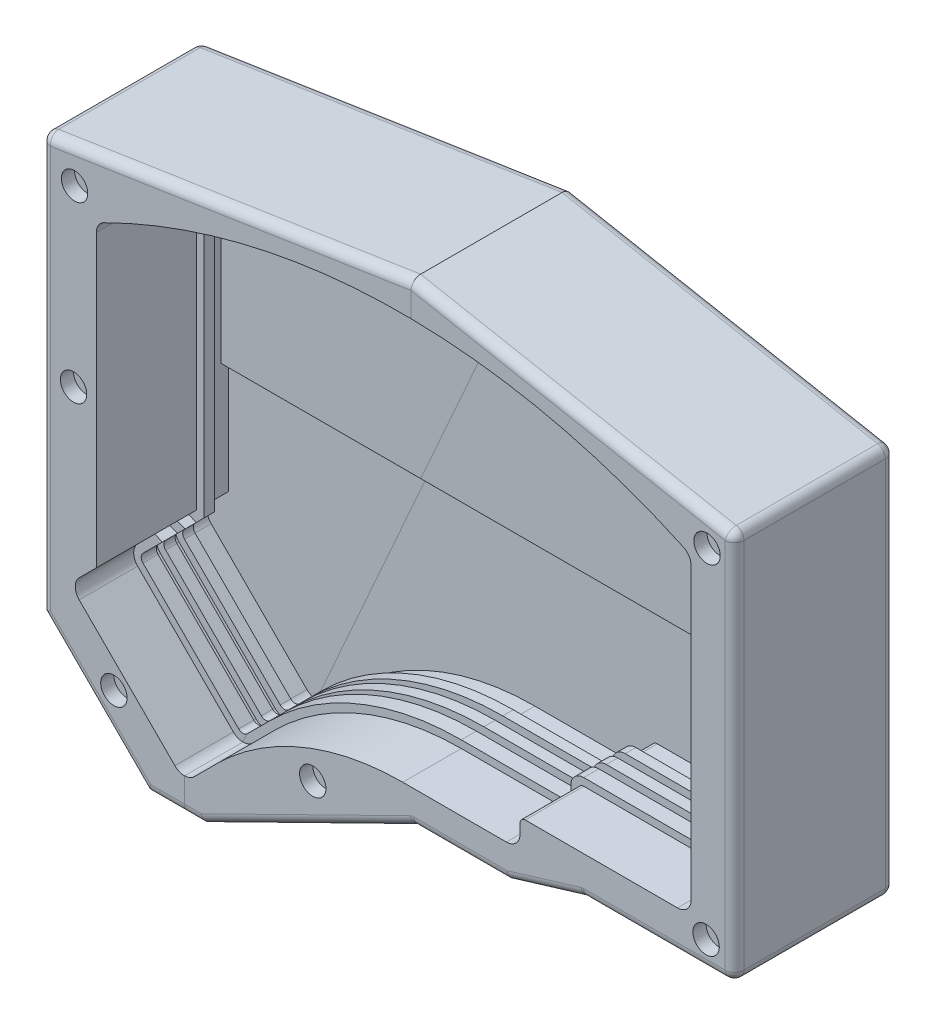
SolidWorks part; units mm, degrees
ref_plane "Front Plane" through (0, 0, 0) normal (0, 0, 1) x (1, 0, 0)
ref_plane "Top Plane" through (0, 0, 0) normal (0, 1, 0) x (1, 0, 0)
ref_plane "Right Plane" through (0, 0, 0) normal (1, 0, 0) x (0, 0, -1)
sketch "Base Drawing" plane through (0, 0, 0) normal (0, 0, 1) x (1, 0, 0)
  line B0 (121.2897, -20.025) -> (161.6756, -20.025)
  line B1 (164.2756, -17.425) -> (164.2756, 59.3777)
  line B2 (8.5386, 57.0643) -> (8.5386, -20.3999)
  line B3 (8.5386, -20.3999) -> (3.6971, -25.2415)
  line B4 (3.6971, -28.9184) -> (29.0822, -54.3036)
  line B5 (32.7591, -54.3036) -> (38.7165, -48.3462)
  line B6 (88.8147, -27.5948) -> (116.2897, -27.5948)
  line B7 (118.8897, -24.9948) -> (118.8897, -22.425)
  circle B8 centre (143.7256, 57.675) radius 1.125
  circle B9 centre (143.7256, 0.525) radius 1.125
  circle B10 centre (64.1715, 70.175) radius 1.125
  circle B11 centre (76.8847, -7.8268) radius 1.125
  circle B12 centre (121.0327, -10.1679) radius 1.125
  circle B13 centre (33.1742, -25.9322) radius 1.125
  arc B14 (161.6756, -20.025) -> (164.2756, -17.425) centre (161.6756, -17.425) ccw
  arc B15 (164.2756, 59.3777) -> (162.7654, 61.7383) centre (161.6756, 59.3777) ccw
  arc B16 (162.7654, 61.7383) -> (9.9768, 59.3903) centre (88.8147, -98.4444) ccw
  arc B17 (9.9768, 59.3903) -> (8.5386, 57.0643) centre (11.1386, 57.0643) ccw
  arc B18 (3.6971, -25.2415) -> (3.6971, -28.9184) centre (5.5355, -27.0799) ccw
  arc B19 (29.0822, -54.3036) -> (32.7591, -54.3036) centre (30.9207, -52.4651) ccw
  arc B20 (88.8147, -27.5948) -> (38.7165, -48.3462) centre (88.8147, -98.4444) ccw
  arc B21 (116.2897, -27.5948) -> (118.8897, -24.9948) centre (116.2897, -24.9948) ccw
  arc B22 (121.2897, -20.025) -> (118.8897, -22.425) centre (121.2897, -22.425) ccw
sketch_block_instance "Block1-1"
sketch_block "Block1"
sketch "Sketch2" plane through (0, 0, 0) normal (0, 0, 1) x (1, 0, 0)
  line L0 (164.2756, 20.9764) -> (176.7756, 20.9764) construction
  line L1 (164.2756, -17.425) -> (164.2756, 59.3777) construction
  line L2 (176.7756, 20.9764) -> (176.7756, 71.7383)
  line L3 (91.0386, 77.9706) -> (30.9207, -55.0651)
  line L4 (91.0386, 77.9706) -> (91.0386, 87.9706)
  line L5 (91.0386, 87.9706) -> (176.7756, 71.7383)
  line L6 (176.7756, 20.9764) -> (176.7756, -31.525)
  line L7 (176.7756, -31.525) -> (136.7756, -31.525)
  line L8 (136.7756, -31.525) -> (136.7756, -37.5948) construction
  line L9 (136.7756, -37.5948) -> (116.7756, -37.5948) construction
  line L10 (116.7756, -37.5948) -> (136.7756, -31.525)
  line L11 (30.9207, -55.0651) -> (30.9207, -65.0651)
  line L12 (116.7756, -37.5948) -> (91.7756, -37.5948)
  line L14 (30.9207, -55.0651) -> (35.9207, -55.0651) construction
  line L15 (-7.0645, 72.9201) -> (91.0386, 87.9706)
  line L16 (-7.0645, -27.0799) -> (-7.0645, 72.9201)
  line L17 (35.9207, -55.0651) -> (35.9207, -65.0651) construction
  line L18 (2.9355, -27.0799) -> (-7.0645, -27.0799) construction
  line L19 (91.7756, -37.5948) -> (35.9207, -65.0651)
  line L20 (-7.0645, -27.0799) -> (-7.0645, -37.0799)
  line L21 (30.9207, -65.0651) -> (20.9207, -65.0651)
  line L22 (20.9207, -65.0651) -> (-7.0645, -37.0799)
  line L23 (35.9207, -65.0651) -> (30.9207, -65.0651)
  arc A0 (162.7654, 61.7383) -> (9.9768, 59.3903) centre (88.8147, -98.4444) ccw construction
  arc A1 (29.0822, -54.3036) -> (32.7591, -54.3036) centre (30.9207, -52.4651) ccw construction
  arc A2 (3.6971, -25.2415) -> (3.6971, -28.9184) centre (5.5355, -27.0799) ccw construction
  dimension "D1" = 12.5
  dimension "D2" = 10
  dimension "D3" = 10
  dimension "D4" = 11.5
  dimension "D5" = 40
  dimension "D6" = 10
  dimension "D7" = 20
  dimension "D8" = 10
  dimension "D9" = 25
  dimension "D10" = 10
  dimension "D11" = 85.737
  dimension "D12" = 100
  dimension "D13" = 10
  dimension "D14" = 10
  dimension "D15" = 5
extrude "Boss-Extrude1" add sketch "Sketch2" along normal blind 35 and the other way blind 7.5 contours L22 L21 L11 L3 L4 L15 L20 | L12 L10 L7 L6 L2 L5 L4 L3 L11 region at (114.4551, 13.7405, 0) region at (31.2356, 22.7834, 0)
ref_plane "Plane1" through (0, 0, 0) normal (0, 0, -1) x (-1, 0, 0)
sketch "Cutout" plane through (0, 0, 0) normal (0, 0, -1) x (-1, 0, 0)
  line L9 (-118.8897, -24.9948) -> (-118.8897, -22.425)
  line L10 (-88.8147, -27.5948) -> (-116.2897, -27.5948)
  line L11 (-32.7591, -54.3036) -> (-38.7165, -48.3462)
  line L12 (-3.6971, -28.9184) -> (-29.0822, -54.3036)
  line L13 (-8.5386, -20.3999) -> (-3.6971, -25.2415)
  line L14 (-8.5386, 57.0643) -> (-8.5386, -20.3999)
  line L15 (-164.2756, -17.425) -> (-164.2756, 59.3777)
  line L16 (-121.2897, -20.025) -> (-161.6756, -20.025)
  line L33 (-88.8147, -27.5948) -> (-88.8147, -28.5948) construction
  line L38 (-165.2756, -17.425) -> (-165.2756, 7.0852) construction
  arc A16 (-121.2897, -20.025) -> (-118.8897, -22.425) centre (-121.2897, -22.425) cw
  arc A17 (-116.2897, -27.5948) -> (-118.8897, -24.9948) centre (-116.2897, -24.9948) cw
  arc A18 (-88.8147, -27.5948) -> (-38.7165, -48.3462) centre (-88.8147, -98.4444) cw
  arc A19 (-29.0822, -54.3036) -> (-32.7591, -54.3036) centre (-30.9207, -52.4651) cw
  arc A20 (-3.6971, -25.2415) -> (-3.6971, -28.9184) centre (-5.5355, -27.0799) cw
  arc A21 (-9.9768, 59.3903) -> (-8.5386, 57.0643) centre (-11.1386, 57.0643) cw
  arc A22 (-162.7654, 61.7383) -> (-9.9768, 59.3903) centre (-88.8147, -98.4444) cw
  arc A23 (-164.2756, 59.3777) -> (-162.7654, 61.7383) centre (-161.6756, 59.3777) cw
  arc A24 (-161.6756, -20.025) -> (-164.2756, -17.425) centre (-161.6756, -17.425) cw
  point P0 (0, 0)
  point P31 (0, 0)
  point P32 (0, 0)
  point P35 (0, 0)
  point P38 (0, 0)
  point P39 (0, 0)
  point P60 (0, 0)
  line B0 (-2.9899, -29.6255) -> (-28.3751, -55.0107)
  line B1 (-33.4663, -55.0107) -> (-39.4236, -49.0533)
  line B2 (-88.8147, -28.5948) -> (-116.2897, -28.5948)
  line B3 (-119.8897, -24.9948) -> (-119.8897, -22.425)
  line B4 (-121.2897, -21.025) -> (-161.6756, -21.025)
  line B5 (-165.2756, -17.425) -> (-165.2756, 59.3777)
  line B6 (-7.5386, 57.0643) -> (-7.5386, -19.9857)
  line B7 (-7.5386, -19.9857) -> (-2.9899, -24.5344)
  arc B8 (-28.3751, -55.0107) -> (-33.4663, -55.0107) centre (-30.9207, -52.4651) cw
  arc B9 (-88.8147, -28.5948) -> (-39.4236, -49.0533) centre (-88.8147, -98.4444) cw
  arc B10 (-116.2897, -28.5948) -> (-119.8897, -24.9948) centre (-116.2897, -24.9948) cw
  arc B11 (-121.2897, -21.025) -> (-119.8897, -22.425) centre (-121.2897, -22.425) cw
  arc B12 (-161.6756, -21.025) -> (-165.2756, -17.425) centre (-161.6756, -17.425) cw
  arc B13 (-165.2756, 59.3777) -> (-163.1846, 62.6462) centre (-161.6756, 59.3777) cw
  arc B14 (-163.1846, 62.6462) -> (-9.53, 60.2849) centre (-88.8147, -98.4444) cw
  arc B15 (-9.53, 60.2849) -> (-7.5386, 57.0643) centre (-11.1386, 57.0643) cw
  arc B16 (-2.9899, -24.5344) -> (-2.9899, -29.6255) centre (-5.5355, -27.0799) cw
sketch_block_instance "Block2-1"
sketch_block "Block2"
extrude "Cut-Extrude1" cut sketch "Cutout" against normal through all contours A24 L16 A16 L9 A17 L10 A18 L11 A19 L12 A20 L13 L14 A21 A22 A23 L15 | B16 B7 B6 B15 B14 B13 B5 L15 A23 A22 A21 L14 L13 A20 L12 A19 L11 A18 L10 A17 L9 A16 L16 A24 B12 B4 B11 B3 B10 B2 B9 B1 B8 B0 region at (82.4187, 19.9301, 0) region at (15.8324, -42.1682, 0)
sketch "Sketch7" plane through (0, 0, 0) normal (0, 0, 1) x (1, 0, 0)
  line L0 (165.2756, 47.675) -> (86.5317, 47.675)
  line L1 (165.2756, -17.425) -> (165.2756, 59.3777) construction
  line L3 (70.3666, 10.525) -> (165.2756, 10.525)
  line L5 (143.7256, 0.525) -> (143.7256, 10.525) construction
  line L6 (143.7256, 57.675) -> (143.7256, 47.675) construction
  line L7 (165.2756, 47.675) -> (165.2756, 10.525)
  line L8 (86.5317, 47.675) -> (7.5386, 47.675)
  line L9 (7.5386, 57.0643) -> (7.5386, -19.9857) construction
  line L10 (7.5386, 47.675) -> (7.5386, 10.525)
  line L11 (7.5386, 10.525) -> (70.3666, 10.525)
  dimension "D2" = 10
extrude "Boss-Extrude2" add sketch "Sketch7" along normal blind 2
ref_plane "Plane2" through (0, 0, 5.7) normal (0, 0, 1) x (1, 0, 0)
sketch "Sketch8" plane through (0, 0, 5.7) normal (0, 0, 1) x (1, 0, 0)
  line L0 (2.9899, -29.6255) -> (28.3751, -55.0107)
  line L1 (33.4663, -55.0107) -> (39.4236, -49.0533)
  line L2 (88.8147, -28.5948) -> (116.2897, -28.5948)
  line L3 (119.8897, -24.9948) -> (119.8897, -22.425)
  line L4 (121.2897, -21.025) -> (161.6756, -21.025)
  line L5 (165.2756, -17.425) -> (165.2756, 59.3777)
  line L6 (7.5386, 57.0643) -> (7.5386, -19.9857)
  line L7 (7.5386, -19.9857) -> (2.9899, -24.5344)
  line L8 (32.052, -53.5965) -> (38.0094, -47.6391)
  line L9 (4.4042, -28.2113) -> (29.7893, -53.5965)
  line L10 (9.5386, -20.8141) -> (4.4042, -25.9486)
  line L11 (9.5386, 57.0643) -> (9.5386, -20.8141)
  line L12 (163.2756, -17.425) -> (163.2756, 59.3777)
  line L13 (121.2897, -19.025) -> (161.6756, -19.025)
  line L14 (117.8897, -24.9948) -> (117.8897, -22.425)
  line L15 (88.8147, -26.5948) -> (116.2897, -26.5948)
  arc A0 (28.3751, -55.0107) -> (33.4663, -55.0107) centre (30.9207, -52.4651) ccw
  arc A1 (88.8147, -28.5948) -> (39.4236, -49.0533) centre (88.8147, -98.4444) ccw
  arc A2 (116.2897, -28.5948) -> (119.8897, -24.9948) centre (116.2897, -24.9948) ccw
  arc A3 (121.2897, -21.025) -> (119.8897, -22.425) centre (121.2897, -22.425) ccw
  arc A4 (161.6756, -21.025) -> (165.2756, -17.425) centre (161.6756, -17.425) ccw
  arc A5 (165.2756, 59.3777) -> (163.1846, 62.6462) centre (161.6756, 59.3777) ccw
  arc A6 (163.1846, 62.6462) -> (9.53, 60.2849) centre (88.8147, -98.4444) ccw
  arc A7 (9.53, 60.2849) -> (7.5386, 57.0643) centre (11.1386, 57.0643) ccw
  arc A8 (2.9899, -24.5344) -> (2.9899, -29.6255) centre (5.5355, -27.0799) ccw
  arc A9 (88.8147, -26.5948) -> (38.0094, -47.6391) centre (88.8147, -98.4444) ccw
  arc A10 (29.7893, -53.5965) -> (32.052, -53.5965) centre (30.9207, -52.4651) ccw
  arc A11 (4.4042, -25.9486) -> (4.4042, -28.2113) centre (5.5355, -27.0799) ccw
  arc A12 (10.4237, 58.4957) -> (9.5386, 57.0643) centre (11.1386, 57.0643) ccw
  arc A13 (162.3463, 60.8304) -> (10.4237, 58.4957) centre (88.8147, -98.4444) ccw
  arc A14 (163.2756, 59.3777) -> (162.3463, 60.8304) centre (161.6756, 59.3777) ccw
  arc A15 (161.6756, -19.025) -> (163.2756, -17.425) centre (161.6756, -17.425) ccw
  arc A16 (121.2897, -19.025) -> (117.8897, -22.425) centre (121.2897, -22.425) ccw
  arc A17 (116.2897, -26.5948) -> (117.8897, -24.9948) centre (116.2897, -24.9948) ccw
  point P0 (88.8147, -98.4444)
  dimension "D1" = 2
extrude "Acrylic Holder" add sketch "Sketch8" along normal blind 2.8
ref_plane "Plane3" through (0, 0, 10.5) normal (0, 0, 1) x (1, 0, 0)
sketch "Sketch9" plane through (0, 0, 10.5) normal (0, 0, 1) x (1, 0, 0)
  line L0 (2.9899, -29.6255) -> (28.3751, -55.0107)
  line L1 (33.4663, -55.0107) -> (39.4236, -49.0533)
  line L2 (88.8147, -28.5948) -> (116.2897, -28.5948)
  line L3 (119.8897, -24.9948) -> (119.8897, -22.425)
  line L4 (121.2897, -21.025) -> (161.6756, -21.025)
  line L5 (165.2756, -17.425) -> (165.2756, 59.3777)
  line L6 (7.5386, 57.0643) -> (7.5386, -19.9857)
  line L7 (7.5386, -19.9857) -> (2.9899, -24.5344)
  line L8 (32.052, -53.5965) -> (38.0094, -47.6391)
  line L9 (4.4042, -28.2113) -> (29.7893, -53.5965)
  line L10 (9.5386, -20.8141) -> (4.4042, -25.9486)
  line L11 (9.5386, 57.0643) -> (9.5386, -20.8141)
  line L12 (163.2756, -17.425) -> (163.2756, 59.3777)
  line L13 (121.2897, -19.025) -> (161.6756, -19.025)
  line L14 (117.8897, -24.9948) -> (117.8897, -22.425)
  line L15 (88.8147, -26.5948) -> (116.2897, -26.5948)
  arc A0 (28.3751, -55.0107) -> (33.4663, -55.0107) centre (30.9207, -52.4651) ccw
  arc A1 (88.8147, -28.5948) -> (39.4236, -49.0533) centre (88.8147, -98.4444) ccw
  arc A2 (116.2897, -28.5948) -> (119.8897, -24.9948) centre (116.2897, -24.9948) ccw
  arc A3 (121.2897, -21.025) -> (119.8897, -22.425) centre (121.2897, -22.425) ccw
  arc A4 (161.6756, -21.025) -> (165.2756, -17.425) centre (161.6756, -17.425) ccw
  arc A5 (165.2756, 59.3777) -> (163.1846, 62.6462) centre (161.6756, 59.3777) ccw
  arc A6 (163.1846, 62.6462) -> (9.53, 60.2849) centre (88.8147, -98.4444) ccw
  arc A7 (9.53, 60.2849) -> (7.5386, 57.0643) centre (11.1386, 57.0643) ccw
  arc A8 (2.9899, -24.5344) -> (2.9899, -29.6255) centre (5.5355, -27.0799) ccw
  arc A9 (88.8147, -26.5948) -> (38.0094, -47.6391) centre (88.8147, -98.4444) ccw
  arc A10 (29.7893, -53.5965) -> (32.052, -53.5965) centre (30.9207, -52.4651) ccw
  arc A11 (4.4042, -25.9486) -> (4.4042, -28.2113) centre (5.5355, -27.0799) ccw
  arc A12 (10.4237, 58.4957) -> (9.5386, 57.0643) centre (11.1386, 57.0643) ccw
  arc A13 (162.3463, 60.8304) -> (10.4237, 58.4957) centre (88.8147, -98.4444) ccw
  arc A14 (163.2756, 59.3777) -> (162.3463, 60.8304) centre (161.6756, 59.3777) ccw
  arc A15 (161.6756, -19.025) -> (163.2756, -17.425) centre (161.6756, -17.425) ccw
  arc A16 (121.2897, -19.025) -> (117.8897, -22.425) centre (121.2897, -22.425) ccw
  arc A17 (116.2897, -26.5948) -> (117.8897, -24.9948) centre (116.2897, -24.9948) ccw
  point P0 (88.8147, -98.4444)
  dimension "D1" = 2
extrude "PCB Holder" add sketch "Sketch9" along normal blind 3
ref_plane "Plane4" through (0, 0, 15.5) normal (0, 0, 1) x (1, 0, 0)
sketch "Sketch10" plane through (0, 0, 15.5) normal (0, 0, 1) x (1, 0, 0)
  line L0 (2.9899, -29.6255) -> (28.3751, -55.0107)
  line L1 (33.4663, -55.0107) -> (39.4236, -49.0533)
  line L2 (88.8147, -28.5948) -> (116.2897, -28.5948)
  line L3 (119.8897, -24.9948) -> (119.8897, -22.425)
  line L4 (121.2897, -21.025) -> (161.6756, -21.025)
  line L5 (165.2756, -17.425) -> (165.2756, 59.3777)
  line L6 (7.5386, 57.0643) -> (7.5386, -19.9857)
  line L7 (7.5386, -19.9857) -> (2.9899, -24.5344)
  line L8 (32.052, -53.5965) -> (38.0094, -47.6391)
  line L9 (4.4042, -28.2113) -> (29.7893, -53.5965)
  line L10 (9.5386, -20.8141) -> (4.4042, -25.9486)
  line L11 (9.5386, 57.0643) -> (9.5386, -20.8141)
  line L12 (163.2756, -17.425) -> (163.2756, 59.3777)
  line L13 (121.2897, -19.025) -> (161.6756, -19.025)
  line L14 (117.8897, -24.9948) -> (117.8897, -22.425)
  line L15 (88.8147, -26.5948) -> (116.2897, -26.5948)
  arc A0 (28.3751, -55.0107) -> (33.4663, -55.0107) centre (30.9207, -52.4651) ccw
  arc A1 (88.8147, -28.5948) -> (39.4236, -49.0533) centre (88.8147, -98.4444) ccw
  arc A2 (116.2897, -28.5948) -> (119.8897, -24.9948) centre (116.2897, -24.9948) ccw
  arc A3 (121.2897, -21.025) -> (119.8897, -22.425) centre (121.2897, -22.425) ccw
  arc A4 (161.6756, -21.025) -> (165.2756, -17.425) centre (161.6756, -17.425) ccw
  arc A5 (165.2756, 59.3777) -> (163.1846, 62.6462) centre (161.6756, 59.3777) ccw
  arc A6 (163.1846, 62.6462) -> (9.53, 60.2849) centre (88.8147, -98.4444) ccw
  arc A7 (9.53, 60.2849) -> (7.5386, 57.0643) centre (11.1386, 57.0643) ccw
  arc A8 (2.9899, -24.5344) -> (2.9899, -29.6255) centre (5.5355, -27.0799) ccw
  arc A9 (88.8147, -26.5948) -> (38.0094, -47.6391) centre (88.8147, -98.4444) ccw
  arc A10 (29.7893, -53.5965) -> (32.052, -53.5965) centre (30.9207, -52.4651) ccw
  arc A11 (4.4042, -25.9486) -> (4.4042, -28.2113) centre (5.5355, -27.0799) ccw
  arc A12 (10.4237, 58.4957) -> (9.5386, 57.0643) centre (11.1386, 57.0643) ccw
  arc A13 (162.3463, 60.8304) -> (10.4237, 58.4957) centre (88.8147, -98.4444) ccw
  arc A14 (163.2756, 59.3777) -> (162.3463, 60.8304) centre (161.6756, 59.3777) ccw
  arc A15 (161.6756, -19.025) -> (163.2756, -17.425) centre (161.6756, -17.425) ccw
  arc A16 (121.2897, -19.025) -> (117.8897, -22.425) centre (121.2897, -22.425) ccw
  arc A17 (116.2897, -26.5948) -> (117.8897, -24.9948) centre (116.2897, -24.9948) ccw
  point P0 (88.8147, -98.4444)
  dimension "D1" = 2
extrude "Aluminum Plate Holder" add sketch "Sketch10" along normal blind 4
sketch "Sketch11" plane through (0, 0, 35) normal (0, 0, 1) x (1, 0, 0)
  line L0 (91.0386, 87.9706) -> (91.0386, 78.9707)
  line L1 (91.0386, 78.9707) -> (30.9207, -56.0651)
  line L2 (30.9207, -56.0651) -> (30.9207, -65.0651)
  line L3 (35.9207, -65.0651) -> (20.9207, -65.0651) construction
  arc A0 (163.1846, 62.6462) -> (9.53, 60.2849) centre (88.8147, -98.4444) ccw construction
  arc A1 (28.3751, -55.0107) -> (33.4663, -55.0107) centre (30.9207, -52.4651) ccw construction
  point P6 (0, 0)
fillet "Fillet2" radius 2.5 23 edges at (156.7756, -31.525, -7.5) (104.2756, -37.5948, -7.5) (126.7756, -34.5599, -7.5) (133.9071, 79.8545, -7.5) (176.7756, 20.1067, -7.5) (176.7756, 71.7383, 13.75) (176.7756, -31.525, 13.75) (28.4207, -65.0651, -7.5) (6.9281, -51.0725, -7.5) (41.9871, 80.4453, -7.5) (-7.0645, 17.9201, -7.5) (-7.0645, 72.9201, 13.75) (41.9871, 80.4453, 35) (133.9071, 79.8545, 35) (176.7756, 20.1067, 35) (156.7756, -31.525, 35) (126.7756, -34.5599, 35) (104.2756, -37.5948, 35) (28.4207, -65.0651, 35) (6.9281, -51.0725, 35) (-7.0645, 17.9201, 35) (63.8481, -51.33, -7.5) (63.8481, -51.33, 35)
sketch "Sketch12" plane through (0, 0, 35) normal (0, 0, 1) x (1, 0, 0)
  line L0 (15.6825, -42.3181) -> (8.6959, -49.3047)
  line L1 (2.9899, -29.6255) -> (28.3751, -55.0107) construction
  line L2 (-4.5645, -36.0444) -> (21.9562, -62.5651) construction
  line L3 (7.5386, 18.5393) -> (-4.5645, 18.5393)
  line L4 (7.5386, 57.0643) -> (7.5386, -19.9857) construction
  line L5 (-4.5645, 70.7743) -> (-4.5645, -36.0444) construction
  line L6 (164.2212, -19.9706) -> (174.2756, -29.025)
  line L7 (136.7756, -29.025) -> (174.2756, -29.025) construction
  line L8 (164.7081, 61.3178) -> (174.2756, 69.6672)
  line L9 (174.2756, -29.025) -> (174.2756, 69.6672) construction
  line L10 (8.0767, 58.9576) -> (-4.5645, 70.7743)
  line L11 (176.7756, 69.6672) -> (174.2756, 69.6672) construction
  line L12 (62.0845, -33.9118) -> (67.7637, -46.6182)
  line L13 (35.3392, -62.5651) -> (90.6723, -35.3515) construction
  circle A0 centre (12.1892, -45.8114) radius 3.5
  circle A1 centre (1.4871, 18.5393) radius 3.5
  arc A2 (161.6756, -21.025) -> (165.2756, -17.425) centre (161.6756, -17.425) ccw construction
  circle A3 centre (169.2484, -24.4978) radius 3.5
  arc A4 (165.2756, 59.3777) -> (163.1846, 62.6462) centre (161.6756, 59.3777) ccw construction
  circle A5 centre (169.4919, 65.4925) radius 3.5
  arc A6 (9.53, 60.2849) -> (7.5386, 57.0643) centre (11.1386, 57.0643) ccw construction
  circle A7 centre (1.7561, 64.866) radius 3.5
  arc A8 (88.8147, -28.5948) -> (39.4236, -49.0533) centre (88.8147, -98.4444) ccw construction
  circle A9 centre (64.9241, -40.265) radius 3.5
  point P51 (0, 0)
  point P52 (0, 0)
  point P55 (0, 0)
  dimension "D2" = 7
extrude "Cut-Extrude4" cut sketch "Sketch12" against normal blind 3.5 contours L10 A7 | L10 A7 | L3 A1 | L3 A1 | L0 A0 | L0 A0 | L12 A9 | L12 A9 | L6 A3 | L6 A3 | L8 A5 | L8 A5 region at (13.2396, -46.8618, 35) region at (11.1388, -44.7611, 35) region at (1.4871, 17.0539, 35) region at (1.4871, 20.0248, 35) region at (170.2424, -23.394, 35) region at (168.2544, -25.6016, 35) region at (168.5152, 66.6117, 35) region at (170.4686, 64.3733, 35) region at (0.7417, 63.7808, 35) region at (2.7705, 65.9511, 35) region at (66.2802, -39.6589, 35) region at (63.568, -40.8712, 35)
sketch "Sketch13" plane through (0, 0, 19.5) normal (0, 0, 1) x (1, 0, 0)
  line L0 (2.9899, -29.6255) -> (28.3751, -55.0107)
  line L1 (33.4663, -55.0107) -> (39.4236, -49.0533)
  line L2 (88.8147, -28.5948) -> (116.2897, -28.5948)
  line L3 (119.8897, -24.9948) -> (119.8897, -22.425)
  line L4 (121.2897, -21.025) -> (161.6756, -21.025)
  line L5 (165.2756, -17.425) -> (165.2756, 59.3777)
  line L6 (7.5386, 57.0643) -> (7.5386, -19.9857)
  line L7 (7.5386, -19.9857) -> (2.9899, -24.5344)
  line L8 (32.052, -53.5965) -> (38.0094, -47.6391)
  line L9 (4.4042, -28.2113) -> (29.7893, -53.5965)
  line L10 (9.5386, -20.8141) -> (4.4042, -25.9486)
  line L11 (9.5386, 57.0643) -> (9.5386, -20.8141)
  line L12 (163.2756, -17.425) -> (163.2756, 59.3777)
  line L13 (121.2897, -19.025) -> (161.6756, -19.025)
  line L14 (117.8897, -24.9948) -> (117.8897, -22.425)
  line L15 (88.8147, -26.5948) -> (116.2897, -26.5948)
  line L16 (7.5386, 57.0643) -> (42.5386, 57.0643) construction
  line L17 (42.5386, 57.0643) -> (42.5386, 72.8436) construction
  line L26 (42.5386, 72.8436) -> (50.9233, 72.8436)
  line L27 (7.5386, -19.9857) -> (9.5386, -20.8141)
  arc A0 (28.3751, -55.0107) -> (33.4663, -55.0107) centre (30.9207, -52.4651) ccw
  arc A1 (88.8147, -28.5948) -> (39.4236, -49.0533) centre (88.8147, -98.4444) ccw
  arc A2 (116.2897, -28.5948) -> (119.8897, -24.9948) centre (116.2897, -24.9948) ccw
  arc A3 (121.2897, -21.025) -> (119.8897, -22.425) centre (121.2897, -22.425) ccw
  arc A4 (161.6756, -21.025) -> (165.2756, -17.425) centre (161.6756, -17.425) ccw
  arc A5 (165.2756, 59.3777) -> (163.1846, 62.6462) centre (161.6756, 59.3777) ccw
  arc A6 (163.1846, 62.6462) -> (9.53, 60.2849) centre (88.8147, -98.4444) ccw
  arc A7 (9.53, 60.2849) -> (7.5386, 57.0643) centre (11.1386, 57.0643) ccw
  arc A8 (2.9899, -24.5344) -> (2.9899, -29.6255) centre (5.5355, -27.0799) ccw
  arc A9 (88.8147, -26.5948) -> (38.0094, -47.6391) centre (88.8147, -98.4444) ccw
  arc A10 (29.7893, -53.5965) -> (32.052, -53.5965) centre (30.9207, -52.4651) ccw
  arc A11 (4.4042, -25.9486) -> (4.4042, -28.2113) centre (5.5355, -27.0799) ccw
  arc A12 (10.4237, 58.4957) -> (9.5386, 57.0643) centre (11.1386, 57.0643) ccw
  arc A13 (162.3463, 60.8304) -> (10.4237, 58.4957) centre (88.8147, -98.4444) ccw
  arc A14 (163.2756, 59.3777) -> (162.3463, 60.8304) centre (161.6756, 59.3777) ccw
  arc A15 (161.6756, -19.025) -> (163.2756, -17.425) centre (161.6756, -17.425) ccw
  arc A16 (121.2897, -19.025) -> (117.8897, -22.425) centre (121.2897, -22.425) ccw
  arc A17 (116.2897, -26.5948) -> (117.8897, -24.9948) centre (116.2897, -24.9948) ccw
  point P0 (88.8147, -98.4444)
  arc M43 (163.1846, 62.6462) -> (9.53, 60.2849) centre (88.8147, -98.4444) ccw
  arc M44 (9.53, 60.2849) -> (7.5386, 57.0643) centre (11.1386, 57.0643) ccw
  line M45 (7.5386, 57.0643) -> (7.5386, -19.9857)
  line M55 (9.5386, -20.8141) -> (9.5386, 57.0643)
  arc M56 (9.5386, 57.0643) -> (10.4237, 58.4957) centre (11.1386, 57.0643) cw
  arc M57 (10.4237, 58.4957) -> (162.3463, 60.8304) centre (88.8147, -98.4444) cw
  dimension "D1" = 35
extrude "Cut-Extrude7" cut sketch "Sketch13" against normal blind 9 contours L27 L26 M45 M55 M56 M57 M43 M44 region at (8.5708, 18.5393, 19.5)
split "Split1" trim tools "Sketch11" bodies to split 113 resulting bodies 108 109
